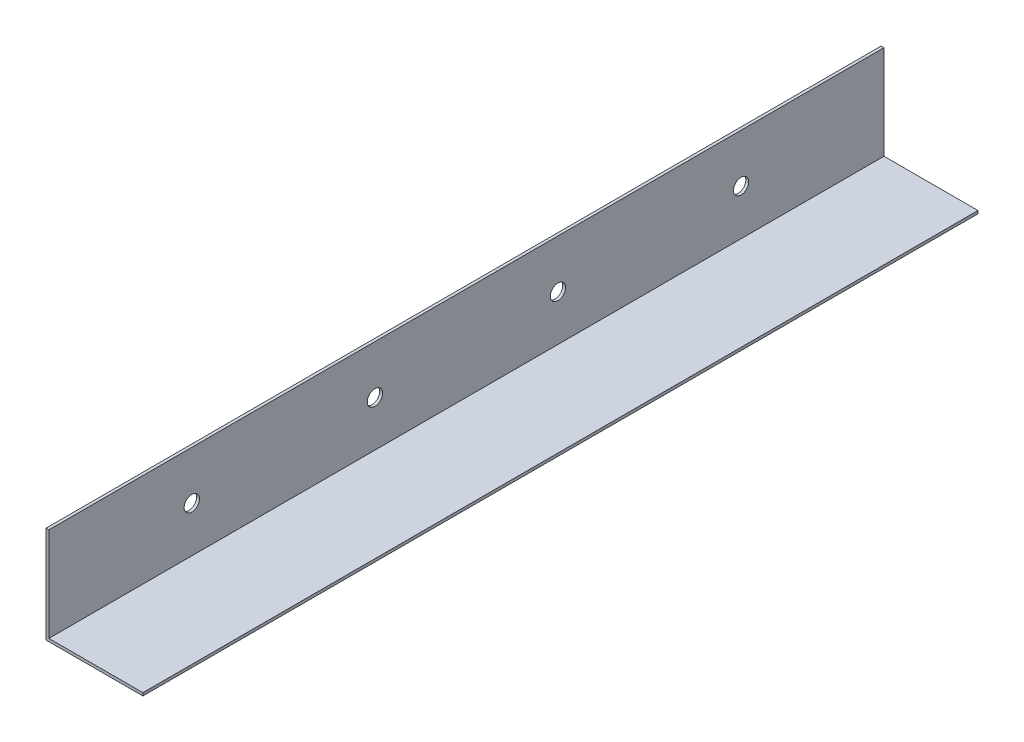
SolidWorks part; units mm, degrees
material "AISI 1015 Acero estirado en frío (SS)"
ref_plane "Alzado" through (0, 0, 0) normal (0, 0, 1) x (1, 0, 0)
ref_plane "Planta" through (0, 0, 0) normal (0, 1, 0) x (1, 0, 0)
ref_plane "Vista lateral" through (0, 0, 0) normal (1, 0, 0) x (0, 0, -1)
sketch "Croquis1" plane through (0, 0, 0) normal (0, 0, 1) x (1, 0, 0)
  line L0 (0, 0) -> (0, 50.8)
  line L1 (0, 0) -> (50.8, 0)
  line L2 (1.5, 1.5) -> (50.8, 1.5)
  line L3 (1.5, 1.5) -> (1.5, 50.8)
  line L4 (0, 50.8) -> (1.5, 50.8)
  line L5 (50.8, 1.5) -> (50.8, 0)
  dimension "D1" = 50.8
  dimension "D2" = 1.5
extrude "Saliente-Extruir1" add sketch "Croquis1" along normal blind 437.896
sketch "Croquis2" plane through (0, 0, 0) normal (-1, 0, 0) x (0, 0, 1)
  line L0 (0, 25.4) -> (437.896, 25.4) construction
  line L1 (0, 50.8) -> (0, 0) construction
  line L2 (437.896, 50.8) -> (437.896, 0) construction
  line L3 (218.948, 50.8) -> (218.948, 0) construction
  line L4 (437.896, 50.8) -> (0, 50.8) construction
  line L5 (437.896, 0) -> (0, 0) construction
  circle A0 centre (266.948, 25.4) radius 4
  circle A1 centre (362.948, 25.4) radius 4
  circle A2 centre (74.948, 25.4) radius 4
  circle A3 centre (170.948, 25.4) radius 4
  point P12 (218.948, 25.4)
  dimension "D3" = 8
  dimension "D1" = 48
  dimension "D2" = 96
extrude "Cortar-Extruir1" cut sketch "Croquis2" against normal blind 4.064
